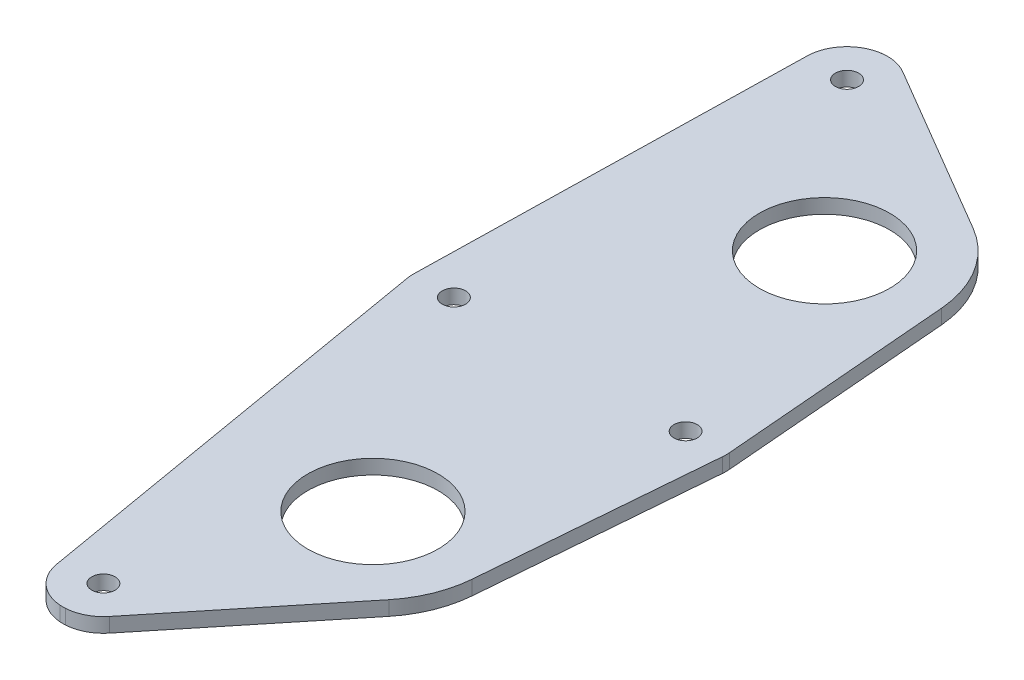
SolidWorks part; units mm, degrees
material "6061-T6 (SS)"
ref_plane "Front" through (0, 0, 0) normal (0, 0, 1) x (1, 0, 0)
ref_plane "Top" through (0, 0, 0) normal (0, 1, 0) x (1, 0, 0)
ref_plane "Right" through (0, 0, 0) normal (1, 0, 0) x (0, 0, -1)
sketch "Sketch1" plane through (0, 0, 0) normal (0, 1, 0) x (1, 0, 0)
  line L0 (0, 49.5046) -> (0, -49.5046) construction
  line L4 (-50.8, 101.6) -> (38.1, 101.6)
  line L5 (-50.8, 101.6) -> (-50.8, -101.6)
  line L6 (-50.8, -101.6) -> (38.1, -101.6)
  line L7 (38.1, 101.6) -> (38.1, -101.6)
  circle A0 centre (0, 49.5046) radius 14.2875
  circle A1 centre (0, -49.5046) radius 14.2875
  circle A4 centre (0, 49.5046) radius 38.1 construction
  circle A5 centre (0, -49.5046) radius 38.1 construction
  point P4 (0, 0)
  point P12 (38.1, 0)
  dimension "D2" = 28.575
  dimension "D3" = 50.8
  dimension "D4" = 76.2
  dimension "D1" = 99.0092
  dimension "D5" = 203.2
extrude "Boss-Extrude1" add sketch "Sketch1" along normal blind 3.175
hole_wizard "#10 Clearance Hole1" positions "Sketch2" profile "Sketch3" hole size "#10" standard "ANSI Inch"
sketch "Sketch2" plane through (0, 3.175, 0) normal (0, 1, 0) x (1, 0, 0)
  line L6 (0, 49.5046) -> (0, -49.5046) construction
  circle A0 centre (0, 49.5046) radius 46.0375 construction
  circle A1 centre (0, -49.5046) radius 46.0375 construction
  circle A3 centre (0, 49.5046) radius 38.1 construction
  circle A6 centre (0, 49.5046) radius 14.2875 construction
  point P2 (19.05, 0)
  point P4 (-29.9949, 84.4296)
  point P10 (-15.875, -92.7184)
  point P40 (-31.75, 0)
  point P74 (-17.7464, -91.9842)
  dimension "D3" = 7.9375
  dimension "D4" = 15.875
  dimension "D1" = 19.05
  dimension "D2" = 31.75
  dimension "D5" = 34.925
sketch "Sketch3" plane through (19.05, 3.175, 0) normal (1, 0, 0) x (0, 0, 1)
  line L0 (0, 0) -> (0, 4.7088)
  line L1 (0, 4.7088) -> (2.5527, 3.175)
  line L2 (2.5527, 3.175) -> (2.5527, 0)
  line L5 (2.5527, 0) -> (0, 0)
  line L10 (0, 4.7088) -> (-2.5527, 3.175) construction
  line L11 (0, -6.35) -> (0, 107.95) construction
  dimension "Hole Dia." = 5.1054
  dimension "Hole Depth" = 3.175
  dimension "Drill Angle" = 118
sketch "Sketch4" plane through (0, 3.175, 0) normal (0, 1, 0) x (1, 0, 0)
  line L0 (12.0665, 70.0335) -> (-25.4837, 92.1047)
  line L1 (-38.8957, 84.6146) -> (-40.6508, 0.185)
  line L2 (-24.65, -94.2209) -> (-40.525, -1.5024)
  line L3 (-8.9629, -98.3293) -> (18.488, -64.5122)
  line L4 (23.7317, 51.465) -> (27.9225, 0.7329)
  line L5 (23.7317, -51.465) -> (27.9225, -0.7329)
  circle A0 centre (0, 49.5046) radius 23.8125 construction
  circle A1 centre (-29.9949, 84.4296) radius 8.9027 construction
  circle A2 centre (-31.75, 0) radius 8.9027 construction
  circle A3 centre (19.05, 0) radius 8.9027 construction
  circle A4 centre (-15.875, -92.7184) radius 8.9027 construction
  circle A5 centre (0, -49.5046) radius 23.8125 construction
  circle A6 centre (-29.9949, 84.4296) radius 2.5527 construction
  circle A7 centre (0, 49.5046) radius 14.2875 construction
  arc A8 (12.0665, 70.0335) -> (23.7317, 51.465) centre (0, 49.5046) cw
  arc A9 (-38.8957, 84.6146) -> (-25.4837, 92.1047) centre (-29.9949, 84.4296) cw
  arc A10 (-8.9629, -98.3293) -> (-24.65, -94.2209) centre (-15.875, -92.7184) cw
  arc A11 (18.488, -64.5122) -> (23.7317, -51.465) centre (0, -49.5046) ccw
  arc A14 (27.9225, -0.7329) -> (27.9225, 0.7329) centre (19.05, 0) ccw
  arc A15 (-40.6508, 0.185) -> (-40.525, -1.5024) centre (-31.75, 0) ccw
  dimension "D1" = 6.35
  dimension "D2" = 9.525
extrude "Cut-Extrude1" cut sketch "Sketch4" against normal through all flip side to cut
